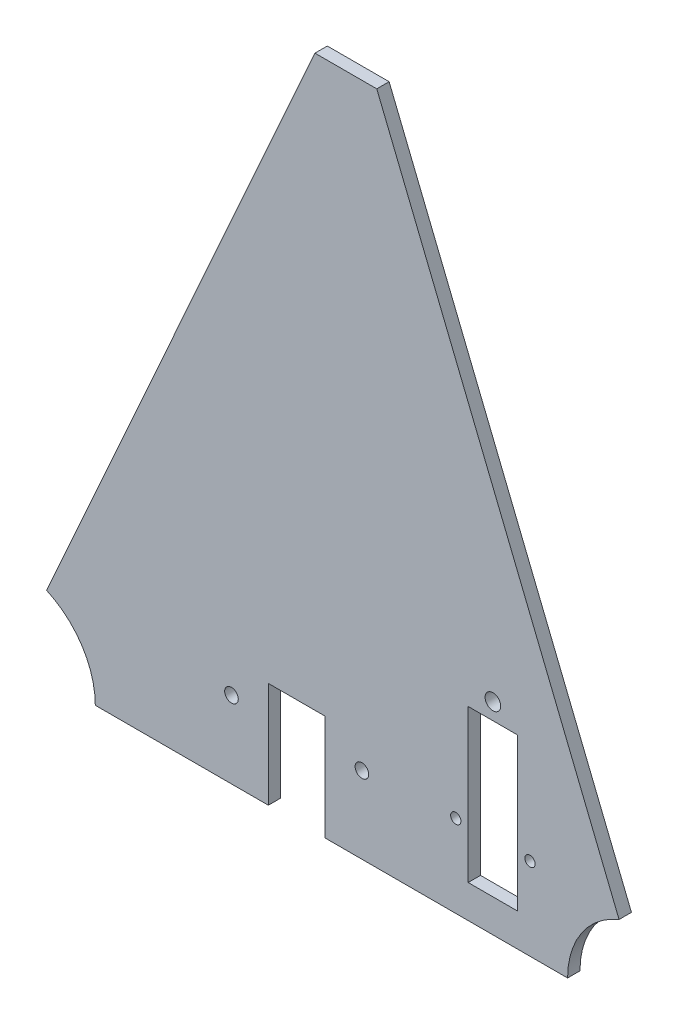
SolidWorks part; units mm, degrees
ref_plane "Front Plane" through (0, 0, 0) normal (0, 0, 1) x (1, 0, 0)
ref_plane "Top Plane" through (0, 0, 0) normal (0, 1, 0) x (1, 0, 0)
ref_plane "Right Plane" through (0, 0, 0) normal (1, 0, 0) x (0, 0, -1)
sketch "Sketch2" plane through (0, 0, 0) normal (0, 0, 1) x (1, 0, 0)
  line L0 (-189.7401, 245.3834) -> (-375.9085, -170.4146)
  line L1 (-375.9085, -170.4146) -> (16.7755, -170.4146)
  line L2 (16.7755, -170.4146) -> (-151.6401, 245.3834)
  line L4 (-189.7401, 245.3834) -> (-151.6401, 245.3834)
  dimension "D1" = 415.798
  dimension "D2" = 415.798
  dimension "D3" = 67.95
  dimension "D4" = 38.1
  dimension "D5" = 392.684
extrude "Boss-Extrude1" add sketch "Sketch2" along normal blind 7.62 contours L0 L1 L2 L4
sketch "Sketch5" plane through (0, 0, 0) normal (0, 0, -1) x (-1, 0, 0)
  circle A0 centre (375.9085, -170.4146) radius 15.875
  dimension "D1" = 31.75
extrude "Cut-Extrude2" cut sketch "Sketch5" against normal blind 50.8
sketch "Sketch6" plane through (0, 0, 0) normal (0, 0, -1) x (-1, 0, 0)
  circle A0 centre (-16.7755, -170.4146) radius 15.875
  dimension "D1" = 31.75
extrude "Cut-Extrude3" cut sketch "Sketch6" against normal blind 50.8 contours A0
ref_plane "Plane1" through (-360.0335, -170.4146, 0) normal (1, 0, 0) x (0, 0, -1)
sketch "Sketch8" plane through (0, 0, 0) normal (0, 0, -1) x (-1, 0, 0)
  line L0 (254.9716, -43.4146) -> (147.0216, -43.4146) construction
  line L1 (360.0335, -170.4146) -> (-0.9005, -170.4146) construction
  line L2 (254.9716, -170.4146) -> (254.9716, 97.7332) construction
  line L3 (254.9716, -43.4146) -> (254.9716, -170.4146) construction
  line L4 (147.0216, -43.4146) -> (147.0216, -170.4146) construction
  line L5 (147.0216, -170.4146) -> (183.5239, -170.4146) construction
  line L6 (183.5239, -170.4146) -> (183.5239, -105.3906) construction
  line L7 (170.6901, 245.3834) -> (179.5665, -170.4146) construction
  line L8 (189.7401, 245.3834) -> (151.6401, 245.3834) construction
  line L9 (183.5239, -105.3906) -> (218.4489, -105.3906) construction
  line L10 (218.4489, -105.3906) -> (218.4489, -170.4146) construction
  line L11 (218.4489, -170.4146) -> (218.4489, -105.3906)
  line L12 (218.4489, -105.3906) -> (183.5239, -105.3906)
  line L13 (183.5239, -105.3906) -> (183.5239, -170.4146)
  line L14 (153.8492, -170.4146) -> (153.8492, -48.647) construction
  dimension "D1" = 268.1478
  dimension "D2" = 107.95
  dimension "D3" = 127
  dimension "D4" = 36.5023
  dimension "D5" = 65.024
  dimension "D6" = 34.925
  dimension "D7" = 121.7676
extrude "Cut-Extrude4" cut sketch "Sketch8" against normal blind 7.62 and the other way through all contours L11 L12 L13
sketch "Sketch9" plane through (0, 0, 0) normal (0, 0, -1) x (-1, 0, 0)
  line L0 (164.9819, -123.0436) -> (183.5239, -123.0436) construction
  line L1 (183.5239, -170.4146) -> (183.5239, -105.3906) construction
  line L2 (160.7909, -127.2346) -> (160.7909, -170.4146) construction
  line L3 (183.5239, -170.4146) -> (-0.9005, -170.4146) construction
  line L4 (236.9909, -123.0436) -> (218.4489, -123.0436) construction
  line L5 (218.4489, -105.3906) -> (218.4489, -170.4146) construction
  line L6 (241.1819, -127.2346) -> (241.1819, -170.4146) construction
  line L7 (360.0335, -170.4146) -> (218.4489, -170.4146) construction
  circle A0 centre (160.7909, -123.0436) radius 4.191
  circle A1 centre (241.1819, -123.0436) radius 4.191
  point P20 (160.7909, -140.8236)
  dimension "D3" = 8.382
  dimension "D6" = 8.382
  dimension "D1" = 18.542
  dimension "D2" = 43.18
  dimension "D4" = 18.542
  dimension "D5" = 43.18
sketch "Sketch10" plane through (0, 0, 0) normal (0, 0, -1) x (-1, 0, 0)
  line L0 (218.4489, -110.7541) -> (349.1963, -110.7541) construction
  line L1 (218.4489, -105.3906) -> (218.4489, -170.4146) construction
  line L2 (189.7401, 245.3834) -> (369.4213, -155.9256) construction
  line L3 (7.3895, -110.7541) -> (138.1995, -110.7541) construction
  line L4 (-10.8158, -155.7008) -> (151.6401, 245.3834) construction
  line L5 (64.8263, -170.4146) -> (64.8263, -56.1146) construction
  line L8 (183.5239, -170.4146) -> (-0.9005, -170.4146) construction
  line L9 (64.8263, -56.1146) -> (95.3063, -56.1146) construction
  line L11 (95.3063, -56.1146) -> (95.3063, -170.4146) construction
  line L12 (64.8263, -170.4146) -> (64.8263, -56.1146)
  line L13 (64.8263, -56.1146) -> (95.3063, -56.1146)
  line L14 (95.3063, -56.1146) -> (95.3063, -170.4146)
  line L15 (64.8263, -170.4146) -> (95.3063, -170.4146)
  dimension "D1" = 130.7473
  dimension "D2" = 130.81
  dimension "D3" = 114.3
  dimension "D4" = 30.48
extrude "Cut-Extrude6" cut sketch "Sketch9" against normal up to next
extrude "Cut-Extrude12" cut sketch "Sketch10" against normal blind 25.4 contours L13 L14 L15 L12
sketch "Sketch13" plane through (0, 0, 0) normal (0, 0, -1) x (-1, 0, 0)
  line L0 (80.0663, -56.1146) -> (80.0663, -50.7806) construction
  line L1 (64.8263, -56.1146) -> (95.3063, -56.1146) construction
  line L2 (80.0663, -50.7806) -> (80.0663, -45.9546) construction
  circle A0 centre (80.0663, -45.9546) radius 4.826
  dimension "D3" = 9.652
  dimension "D1" = 5.334
  dimension "D2" = 4.826
extrude "Cut-Extrude13" cut sketch "Sketch13" against normal up to next
sketch "Sketch14" plane through (0, 0, 0) normal (0, 0, -1) x (-1, 0, 0)
  circle A0 centre (-16.7755, -170.4146) radius 50.8
  dimension "D1" = 101.6
extrude "Cut-Extrude14" cut sketch "Sketch14" against normal up to next
sketch "Sketch15" plane through (0, 0, 0) normal (0, 0, -1) x (-1, 0, 0)
  circle A0 centre (375.9085, -170.4146) radius 50.8
  dimension "D1" = 101.6
extrude "Cut-Extrude15" cut sketch "Sketch15" against normal up to next
sketch "Sketch16" plane through (0, 0, 0) normal (0, 0, -1) x (-1, 0, 0)
  line L0 (95.3063, -56.1146) -> (95.3063, -170.4146) construction
  line L1 (95.3063, -150.0946) -> (64.8263, -150.0946)
  line L2 (95.3063, -150.0946) -> (95.3063, -170.4146)
  line L3 (95.3063, -170.4146) -> (64.8263, -170.4146)
  line L4 (64.8263, -150.0946) -> (64.8263, -170.4146)
  dimension "D1" = 20.32
extrude "Boss-Extrude2" add sketch "Sketch16" against normal blind 7.62
sketch "Sketch17" plane through (0, 0, 0) normal (0, 0, -1) x (-1, 0, 0)
  line L0 (64.8263, -150.0946) -> (64.8263, -125.9646) construction
  line L1 (64.8263, -150.0946) -> (64.8263, -56.1146) construction
  line L2 (64.8263, -125.9646) -> (64.8263, -113.2646) construction
  line L3 (64.8263, -113.2646) -> (49.5863, -113.2646) construction
  line L4 (49.5863, -113.2646) -> (49.5863, -125.9646) construction
  line L5 (49.5863, -125.9646) -> (64.8263, -125.9646) construction
  line L6 (49.5863, -119.6146) -> (64.8263, -119.6146) construction
  line L7 (95.3063, -113.2646) -> (110.5463, -113.2646) construction
  line L8 (95.3063, -56.1146) -> (95.3063, -150.0946) construction
  line L9 (110.5463, -113.2646) -> (110.5463, -125.9646) construction
  line L10 (110.5463, -125.9646) -> (95.3063, -125.9646) construction
  line L11 (110.5463, -119.6146) -> (95.3063, -119.6146) construction
  circle A0 centre (57.2063, -119.6146) radius 3.175
  circle A3 centre (102.9263, -119.6146) radius 3.175
  dimension "D4" = 6.35
  dimension "D7" = 6.35
  dimension "D1" = 24.13
  dimension "D2" = 12.7
  dimension "D3" = 15.24
  dimension "D5" = 15.24
  dimension "D6" = 12.7
extrude "Cut-Extrude16" cut sketch "Sketch17" against normal up to next
